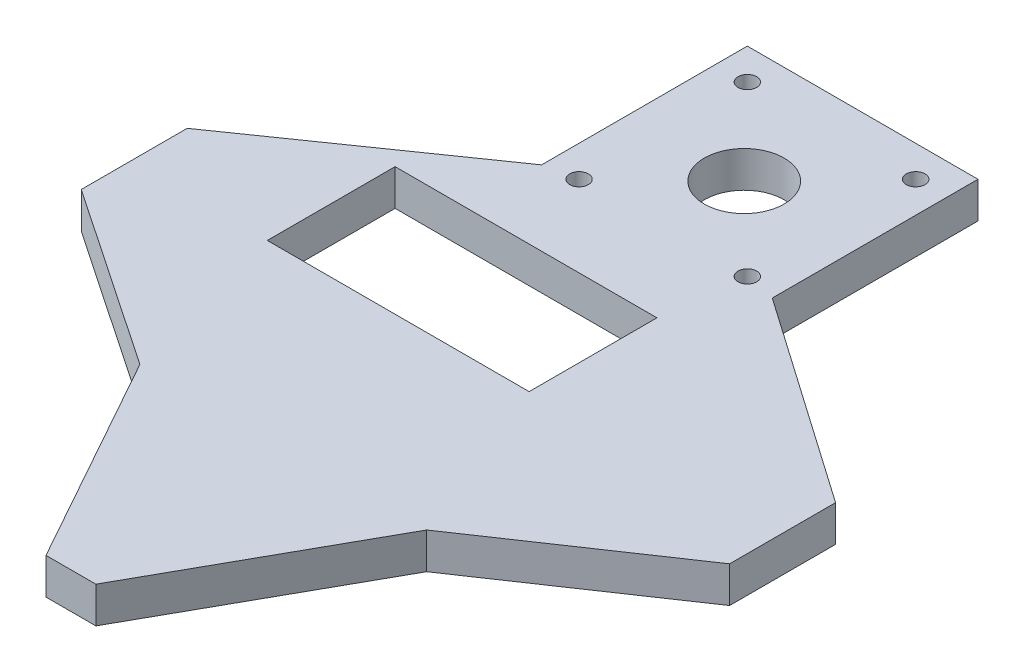
SolidWorks part; units mm, degrees
ref_plane "Plan de face" through (0, 0, 0) normal (0, 0, 1) x (1, 0, 0)
ref_plane "Plan de dessus" through (0, 0, 0) normal (0, 1, 0) x (1, 0, 0)
ref_plane "Plan de droite" through (0, 0, 0) normal (1, 0, 0) x (0, 0, -1)
sketch "Esquisse1" plane through (0, 0, 0) normal (0, 1, 0) x (1, 0, 0)
  line L0 (0, 0) -> (-18.5, 0)
  line L1 (-18.5, 0) -> (-18.5, -33)
  line L2 (-18.5, -33) -> (-52, -56.3453)
  line L3 (-52, -56.3453) -> (-52, -73.3453)
  line L4 (-52, -73.3453) -> (-23, -92.9412)
  line L5 (-23, -92.9412) -> (-4, -127)
  line L6 (-4, -127) -> (0, -127)
  line L12 (0, 0) -> (0, -127)
  dimension "D1" = 33
  dimension "D2" = 18.5
  dimension "D3" = 23
  dimension "D4" = 39
  dimension "D5" = 17
  dimension "D6" = 4
  dimension "D7" = 52
  dimension "D8" = 127
  dimension "D9" = 35
extrude "Boss.-Extru.1" add sketch "Esquisse1" along normal blind 5.8
sketch "Esquisse2" plane through (0, 5.8, 0) normal (0, 1, 0) x (1, 0, 0)
  line L0 (0, -127) -> (0, 0) construction
  line L1 (0, 0) -> (-18.5, 0) construction
  line L2 (-18.5, 0) -> (-18.5, -33) construction
  circle A0 centre (-13.5, -5) radius 1.5
  circle A1 centre (0, -19) radius 6.4
  circle A2 centre (-13.5, -32) radius 1.5
  dimension "D2" = 3
  dimension "D3" = 12.8
  dimension "D6" = 3
  dimension "D1" = 13.5
  dimension "D4" = 19
  dimension "D5" = 5
  dimension "D7" = 27
  dimension "D8" = 5
extrude "Enlèv. mat.-Extru.1" cut sketch "Esquisse2" against normal up to surface (5.8 mm away) up to face at (-21, 0, 63.704)
mirror "Symétrie2" about plane through (0, 5.8, 0) normal (-1, 0, 0) of "Enlèv. mat.-Extru.1", "Boss.-Extru.1"
sketch "Esquisse3" plane through (0, 5.8, 0) normal (0, 1, 0) x (1, 0, 0)
  line L0 (18.5, 0) -> (-18.5, 0) construction
  line L1 (-30, -45) -> (12, -45)
  line L2 (-30, -45) -> (-30, -65.5)
  line L3 (-30, -65.5) -> (12, -65.5)
  line L4 (12, -45) -> (12, -65.5)
  line L5 (-52, -56.3453) -> (-52, -73.3453) construction
  dimension "D1" = 45
  dimension "D2" = 20.5
  dimension "D3" = 42
  dimension "D4" = 22
extrude "Enlèv. mat.-Extru.2" cut sketch "Esquisse3" against normal up to surface (5.8 mm away) up to face at (13.5, 0, 6.5)
